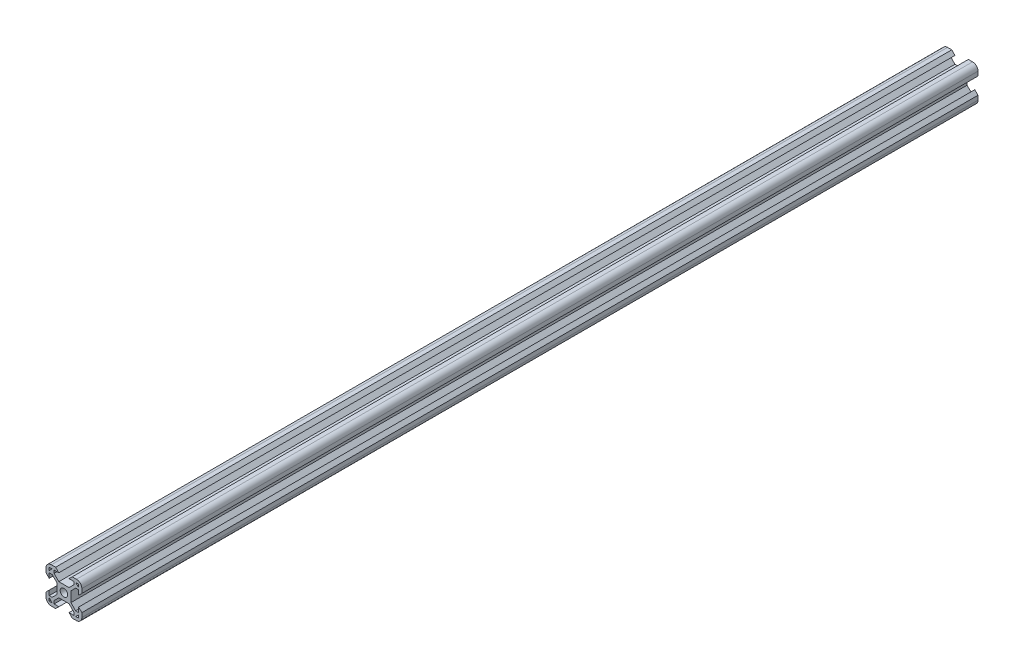
SolidWorks part; units mm, degrees
material "6063-T5"
ref_plane "Front Plane" through (0, 0, 0) normal (0, 0, 1) x (1, 0, 0)
ref_plane "Top Plane" through (0, 0, 0) normal (0, 1, 0) x (1, 0, 0)
ref_plane "Right Plane" through (0, 0, 0) normal (1, 0, 0) x (0, 0, -1)
sketch "Sketch1" plane through (0, 0, 0) normal (0, 0, 1) x (1, 0, 0)
  line L1 (10, -10) -> (-10, -10)
  line L2 (10, -10) -> (10, 10)
  line L3 (10, 10) -> (-10, 10)
  line L4 (-10, -10) -> (-10, 10)
  line L5 (10, -10) -> (-10, 10) construction
  line L6 (10, 10) -> (-10, -10) construction
  point P0 (0, 0)
  dimension "D1" = 20
  dimension "D2" = 20
extrude "Boss-Extrude1" add sketch "Sketch1" against normal blind 500 contours L3 L4 L1 L2
sketch "Sketch2" plane through (0, 0, 0) normal (0, 0, 1) x (1, 0, 0)
  line L0 (-10, 10) -> (10, -10) construction
  line L1 (-10, -10) -> (10, 10) construction
  line L2 (10, 10) -> (-10, 10) construction
  line L3 (-5.4993, -6.56) -> (-2.84, -3.9007)
  line L4 (-2.84, -8.2) -> (-4.64, -10)
  line L5 (10, -10) -> (-10, -10) construction
  line L6 (2.84, -3.9007) -> (5.4993, -6.56)
  line L7 (-5.4993, -6.56) -> (-5.4993, -8.2)
  line L8 (5.4993, -6.56) -> (5.4993, -8.2)
  line L9 (-2.84, -3.9007) -> (2.84, -3.9007)
  line L10 (-5.4993, -8.2) -> (-2.84, -8.2)
  line L11 (2.84, -8.2) -> (4.64, -10)
  line L12 (2.84, -8.2) -> (5.4993, -8.2)
  line L13 (-4.64, -10) -> (4.64, -10)
  dimension "D1" = 1.64
  dimension "D2" = 0.75
  dimension "D3" = 0.75
  dimension "D4" = 5.68
  dimension "D5" = 1.8
extrude "Cut-Extrude2" cut sketch "Sketch2" against normal up to next contours L9 L6 L8 L12 L11 L13 L4 L10 L7 L3
ref_axis "Axis1" through (0, 0, -525) along (0, 0, 1)
pattern_circular "CirPattern1" count 4 over 360 about axis through (0, 0, -525) along (0, 0, 1) of "Cut-Extrude2"
sketch "Sketch3" plane through (0, 0, 0) normal (0, 0, 1) x (1, 0, 0)
  circle A0 centre (0, 0) radius 2.1
  dimension "D1" = 4.2
extrude "Cut-Extrude3" cut sketch "Sketch3" against normal up to next
sketch "Sketch4" plane through (0, 0, 0) normal (0, 0, 1) x (1, 0, 0)
  line L0 (-8.2, 8.2) -> (-8.2, 6.5693)
  line L1 (-8.2, 6.5693) -> (-6.5693, 8.2)
  line L2 (-6.5693, 8.2) -> (-8.2, 8.2)
  line L3 (-8.2, 8.2) -> (-7.3847, 7.3847) construction
  line L4 (-10, 10) -> (0, 0) construction
  line L5 (-6.56, 5.4993) -> (-5.4993, 6.56) construction
  line L6 (-2.84, 8.2) -> (-5.4993, 8.2) construction
  dimension "D1" = 1.07
extrude "Cut-Extrude4" cut sketch "Sketch4" against normal up to next
pattern_circular "CirPattern2" count 4 over 360 about axis through (0, 0, -525) along (0, 0, 1) of "Cut-Extrude4"
fillet "Fillet1" radius 3 4 edges at (-10, -10, -250) (-10, 10, -250) (10, 10, -250) (10, -10, -250)
